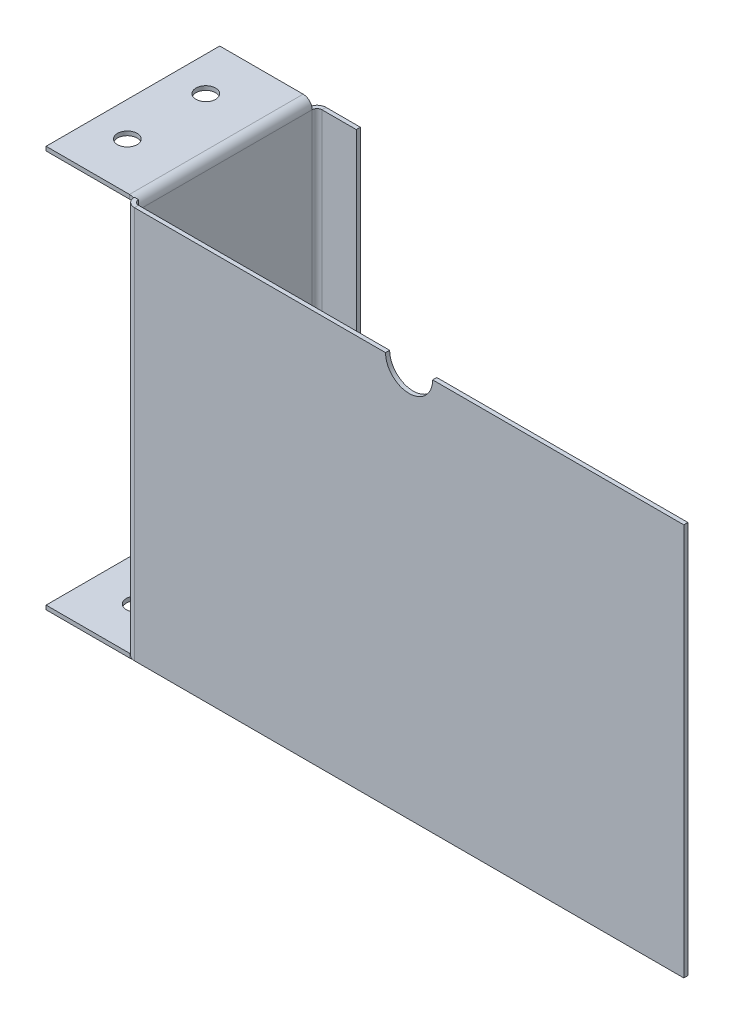
SolidWorks part; units mm, degrees
note: The reader was unsure of these and kept them because the rebuilt part matched: flange length of "Edge-Flange1", "Edge-Flange2", "Edge-Flange3", "Edge-Flange4".
material "Plain Carbon Steel"
ref_plane "Front Plane" through (0, 0, 0) normal (0, 0, 1) x (1, 0, 0)
ref_plane "Top Plane" through (0, 0, 0) normal (0, 1, 0) x (1, 0, 0)
ref_plane "Right Plane" through (0, 0, 0) normal (1, 0, 0) x (0, 0, -1)
sketch "Sketch1" plane through (0, 0, 0) normal (0, 0, 1) x (1, 0, 0)
  line L0 (0, 76.2) -> (355.6, 76.2) construction
  line L1 (0, 0) -> (355.6, 0)
  line L2 (0, 0) -> (0, 254)
  line L3 (0, 254) -> (162.56, 254)
  line L4 (355.6, 0) -> (355.6, 254)
  line L5 (177.8, 254) -> (177.8, 0) construction
  line L6 (193.04, 254) -> (355.6, 254)
  line L7 (162.56, 254) -> (177.8, 254) construction
  line L8 (177.8, 254) -> (193.04, 254) construction
  arc A0 (162.56, 254) -> (193.04, 254) centre (177.8, 254) ccw
  dimension "D4" = 15.24
  dimension "D1" = 355.6
  dimension "D2" = 254
  dimension "D3" = 177.8
base flange "Base-Flange1" sketch "Sketch1" thickness 2.6568 reverse thickness direction no parameters "D1"=3.175
edge flange "Edge-Flange1" sketch "Sketch8" flange angle 90 flange length 115.57 flange position bend outside bend radius 3.175 thickness 2.6568 relief rectangular parameters "D6"=10
sketch "Sketch8" plane through (0, 0, -2.6568) normal (-1, 0, 0) x (0, 1, 0)
  line L0 (254, 0) -> (0, 0) construction
  line L1 (254, 0) -> (0, 0)
  line L2 (0, 0) -> (0, 115.57)
  line L3 (0, 115.57) -> (254, 115.57)
  line L4 (254, 115.57) -> (254, 0)
bend "EdgeBend1" bend radius 3.175 bend angle 90 parameters "D5"=1
edge flange "Edge-Flange2" sketch "Sketch11" flange angle 90 flange length 57.15 flange position material inside bend radius 3.175 thickness 2.6568 relief none parameters "D6"=10
sketch "Sketch11" plane through (-5.8318, 254, 0) normal (0, 1, 0) x (0, 0, -1)
  line L0 (5.8318, 0) -> (118.2268, 0) construction
  line L1 (5.8318, 0) -> (118.2268, 0)
  line L2 (5.8318, 0) -> (5.8318, 57.15)
  line L3 (5.8318, 57.15) -> (118.2268, 57.15)
  line L4 (118.2268, 57.15) -> (118.2268, 0)
bend "EdgeBend2" bend radius 3.175 bend angle 90 parameters "D5"=2
edge flange "Edge-Flange3" sketch "Sketch14" flange angle 90 flange length 57.15 flange position bend outside bend radius 3.175 thickness 2.6568 relief rectangular parameters "D6"=10
sketch "Sketch14" plane through (-5.8318, 0, 0) normal (0, -1, 0) x (0, 0, 1)
  line L0 (-118.2268, 0) -> (-5.8318, 0) construction
  line L1 (-118.2268, 0) -> (-5.8318, 0)
  line L2 (-118.2268, 0) -> (-118.2268, 57.15)
  line L3 (-118.2268, 57.15) -> (-5.8318, 57.15)
  line L4 (-5.8318, 57.15) -> (-5.8318, 0)
bend "EdgeBend3" bend radius 3.175 bend angle 90 parameters "D5"=3
edge flange "Edge-Flange4" sketch "Sketch17" flange angle 90 flange length 25.4 flange position bend outside bend radius 3.175 thickness 2.6568 relief rectangular parameters "D6"=10
sketch "Sketch17" plane through (-3.175, 0, -118.2268) normal (0, 0, 1) x (0, -1, 0)
  line L2 (-248.1682, 0) -> (-248.1682, 25.4)
  line L3 (-248.1682, 25.4) -> (0, 25.4)
  line L4 (0, 25.4) -> (0, 0)
  line L5 (0, 0) -> (-248.1682, 0) construction
  line L6 (0, 0) -> (-248.1682, 0)
bend "EdgeBend4" bend radius 3.175 bend angle 90 parameters "D5"=4
sketch "Sketch22" plane through (0, 254, 0) normal (0, 1, 0) x (1, 0, 0)
  line L0 (-40.7645, 118.2268) -> (-40.7645, 5.8318) construction
  line L1 (-62.9818, 5.8318) -> (-9.0068, 5.8318) construction
  line L2 (-9.0068, 118.2268) -> (-62.9818, 118.2268) construction
  line L3 (-62.9818, 118.2268) -> (-62.9818, 5.8318) construction
  circle A0 centre (-40.7645, 86.995) radius 6.35
  circle A1 centre (-40.7645, 36.195) radius 6.35
  dimension "D2" = 12.7
  dimension "D1" = 22.2174
  dimension "D3" = 50.8
  dimension "D4" = 31.2318
extrude "Cut-Extrude1" cut sketch "Sketch22" along direction (0, -1, 0) on the side against the normal up to next (2.6568 mm away) normal cut yes
sketch "Sketch23" plane through (0, -3.175, 0) normal (0, 1, 0) x (1, 0, 0)
  line L0 (-34.4068, 118.2268) -> (-34.4068, 5.8318) construction
  line L1 (-62.9818, 118.2268) -> (-9.0068, 118.2268) construction
  line L2 (-9.0068, 5.8318) -> (-62.9818, 5.8318) construction
  line L3 (-9.0068, 118.2268) -> (-9.0068, 5.8318) construction
  circle A0 centre (-34.4068, 86.36) radius 6.35
  circle A1 centre (-34.4068, 35.56) radius 6.35
  dimension "D4" = 12.7
  dimension "D1" = 25.4
  dimension "D2" = 50.8
  dimension "D3" = 29.7282
extrude "Cut-Extrude2" cut sketch "Sketch23" along direction (0, 1, 0) on the side against the normal up to next (2.6568 mm away) normal cut yes
sketch "Sketch24" plane through (-5.8318, 0, 0) normal (-1, 0, 0) x (0, 0, 1)
  line L0 (-62.0293, 248.1682) -> (-62.0293, 76.2) construction
  line L1 (-118.2268, 248.1682) -> (-5.8318, 248.1682) construction
  line L2 (-62.0293, 76.2) -> (-62.0293, 41.7932) construction
  line L3 (-118.2268, 41.7932) -> (-5.8318, 41.7932) construction
  line L4 (-118.2268, 248.1682) -> (-118.2268, 0) construction
  line L5 (-5.8318, 248.1682) -> (-5.8318, 0) construction
  line L6 (-118.2268, 254) -> (-5.8318, 254) construction
  circle A0 centre (-86.995, 41.7932) radius 6.35
  circle A1 centre (-34.4068, 41.7932) radius 6.35
  dimension "D3" = 12.7
  dimension "D1" = 177.8
  dimension "D2" = 34.4068
  dimension "D4" = 31.2318
  dimension "D5" = 52.5882
extrude "Cut-Extrude3" cut sketch "Sketch24" along direction (1, 0, 0) on the side against the normal up to next (2.6568 mm away) normal cut yes
sketch "Bend-Lines1" [suppressed] plane through (0, 0, 0) normal (0, 1, 0) x (1, 0, 0)
sketch "Bounding-Box1" [suppressed] plane through (0, 0, 0) normal (0, 1, 0) x (1, 0, 0)
sheet metal parameters "Sheet-Metal1" thickness 2.6568 parameters "D1"=3.175
flat pattern "Flat-Pattern1" [suppressed]
sketch "Bend-Lines2" plane through (0, 0, 0) normal (0, 1, 0) x (1, 0, 0)
sketch3d "Bounding-Box2" [suppressed]
  line L0 (0, 0, 0) -> (-355.6, 0, 0) construction
  line L1 (0, 254, 0) -> (-355.6, 254, 0) construction
  line L2 (0, 0, 0) -> (0, 254, 0) construction
  line L3 (-355.6, 0, 0) -> (-355.6, 254, 0) construction
sheet metal parameters "Sheet-Metal2" thickness 2.6568 parameters "D1"=3.175
flat pattern "Flat-Pattern1"
sketch "Bend-Lines2" plane through (0, 0, 0) normal (0, 0, 1) x (1, 0, 0)
  line L0 (-3.537, 254) -> (-3.537, 0) construction
  line L1 (-3.537, 254) -> (-3.537, 0) construction
sketch3d "Bounding-Box2" [suppressed]
  line L0 (-123.5965, 0, 0) -> (355.6, 0, 0) construction
  line L1 (-123.5965, 254, 0) -> (355.6, 254, 0) construction
  line L2 (-123.5965, 0, 0) -> (-123.5965, 254, 0) construction
  line L3 (355.6, 0, 0) -> (355.6, 254, 0) construction
bend of the flat pattern "Flatten-<EdgeBend1>1"
sheet metal parameters "Sheet-Metal3" thickness 2.6568 parameters "D1"=3.175
flat pattern "Flat-Pattern1"
sketch "Bend-Lines2" plane through (0, 0, 0) normal (0, 0, 1) x (1, 0, 0)
  line L0 (-3.537, 254) -> (-3.537, 0) construction
  line L1 (-3.537, 254) -> (-3.537, 0) construction
  line L2 (-7.074, 251.7051) -> (-123.5965, 251.7051) construction
  line L3 (-7.074, 251.7051) -> (-123.5965, 251.7051) construction
sketch3d "Bounding-Box2" [suppressed]
  line L0 (-123.5965, 0, 0) -> (355.6, 0, 0) construction
  line L1 (-123.5965, 309.2171, 0) -> (355.6, 309.2171, 0) construction
  line L2 (-123.5965, 0, 0) -> (-123.5965, 309.2171, 0) construction
  line L3 (355.6, 0, 0) -> (355.6, 309.2171, 0) construction
bend of the flat pattern "Flatten-<EdgeBend1>1"
bend of the flat pattern "Flatten-<EdgeBend2>1"
sheet metal parameters "Sheet-Metal4" thickness 2.6568 parameters "D1"=3.175
flat pattern "Flat-Pattern1"
sketch "Bend-Lines2" plane through (0, 0, 0) normal (0, 0, 1) x (1, 0, 0)
  line L0 (-3.537, 254) -> (-3.537, 0) construction
  line L1 (-3.537, 254) -> (-3.537, 0) construction
  line L2 (-7.074, 251.7051) -> (-123.5965, 251.7051) construction
  line L3 (-7.074, 251.7051) -> (-123.5965, 251.7051) construction
  line L4 (-123.5965, -3.537) -> (-7.074, -3.537) construction
  line L5 (-123.5965, -3.537) -> (-7.074, -3.537) construction
sketch3d "Bounding-Box2" [suppressed]
  line L0 (-123.5965, -61.049, 0) -> (355.6, -61.049, 0) construction
  line L1 (-123.5965, 309.2171, 0) -> (355.6, 309.2171, 0) construction
  line L2 (-123.5965, -61.049, 0) -> (-123.5965, 309.2171, 0) construction
  line L3 (355.6, -61.049, 0) -> (355.6, 309.2171, 0) construction
bend of the flat pattern "Flatten-<EdgeBend1>1"
bend of the flat pattern "Flatten-<EdgeBend2>1"
bend of the flat pattern "Flatten-<EdgeBend3>1"
sheet metal parameters "Sheet-Metal5" thickness 2.6568 parameters "D1"=3.175
flat pattern "Flat-Pattern1" [suppressed]
sketch "Bend-Lines2" plane through (0, 0, 0) normal (0, 0, 1) x (1, 0, 0)
  line L0 (-3.537, 254) -> (-3.537, 0) construction
  line L1 (-3.537, 254) -> (-3.537, 0) construction
  line L2 (-7.074, 251.7051) -> (-119.469, 251.7051) construction
  line L3 (-7.074, 251.7051) -> (-119.469, 251.7051) construction
  line L4 (-119.469, -3.537) -> (-7.074, -3.537) construction
  line L5 (-119.469, -3.537) -> (-7.074, -3.537) construction
  line L6 (-123.0059, 248.1682) -> (-123.0059, 0) construction
  line L7 (-123.0059, 248.1682) -> (-123.0059, 0) construction
sketch3d "Bounding-Box2" [suppressed]
  line L0 (-326.5679, -315.049, 0) -> (177.8, -315.049, 0) construction
  line L1 (-326.5679, 55.2171, 0) -> (177.8, 55.2171, 0) construction
  line L2 (-326.5679, -315.049, 0) -> (-326.5679, 55.2171, 0) construction
  line L3 (177.8, -315.049, 0) -> (177.8, 55.2171, 0) construction
bend of the flat pattern "Flatten-<EdgeBend1>1"
bend of the flat pattern "Flatten-<EdgeBend2>1"
bend of the flat pattern "Flatten-<EdgeBend3>1"
bend of the flat pattern "Flatten-<EdgeBend4>1"
sketch "Sketch18-1" [suppressed] plane through (-1.2421, 246.2353, 0) normal (0, 0, 1) x (0, -1, 0)
  spline S2 degree 3 poles (-47.1137, -34.925) (-47.1137, -47.625) (-34.4137, -47.625) (-34.4137, -34.925) (-34.4137, -22.225) (-47.1137, -22.225) (-47.1137, -34.925) (-47.1137, -47.625) (-34.4137, -47.625) knots -0.5 0 0 0 0.5 0.5 0.5 1 1 1 1.5 1.5 1.5 weights 1 0.333333 0.333333 1 0.333333 0.333333 1 0.333333 0.333333 only from (-47.1137, -34.925) to (-47.1137, -34.925)
  spline S3 degree 3 poles (-47.1137, -86.995) (-47.1137, -99.695) (-34.4137, -99.695) (-34.4137, -86.995) (-34.4137, -74.295) (-47.1137, -74.295) (-47.1137, -86.995) (-47.1137, -99.695) (-34.4137, -99.695) knots -0.5 0 0 0 0.5 0.5 0.5 1 1 1 1.5 1.5 1.5 weights 1 0.333333 0.333333 1 0.333333 0.333333 1 0.333333 0.333333 only from (-47.1137, -86.995) to (-47.1137, -86.995)
sheet metal parameters "Sheet-Metal8" thickness 2.6568 parameters "D1"=3.175
flat pattern "Flat-Pattern1"
sketch "Bend-Lines2" plane through (0, 0, 0) normal (0, 0, 1) x (1, 0, 0)
  line L0 (-3.537, 254) -> (-3.537, 0) construction
  line L1 (-3.537, 254) -> (-3.537, 0) construction
  line L2 (-7.074, 251.7051) -> (-119.469, 251.7051) construction
  line L3 (-7.074, 251.7051) -> (-119.469, 251.7051) construction
  line L4 (-119.469, -3.537) -> (-7.074, -3.537) construction
  line L5 (-119.469, -3.537) -> (-7.074, -3.537) construction
  line L6 (-123.0059, 248.1682) -> (-123.0059, 0) construction
  line L7 (-123.0059, 248.1682) -> (-123.0059, 0) construction
sketch3d "Bounding-Box2" [suppressed]
  line L0 (-326.5679, -315.049, 0) -> (177.8, -315.049, 0) construction
  line L1 (-326.5679, 55.2171, 0) -> (177.8, 55.2171, 0) construction
  line L2 (-326.5679, -315.049, 0) -> (-326.5679, 55.2171, 0) construction
  line L3 (177.8, -315.049, 0) -> (177.8, 55.2171, 0) construction
bend of the flat pattern "Flatten-<EdgeBend1>1"
bend of the flat pattern "Flatten-<EdgeBend2>1"
bend of the flat pattern "Flatten-<EdgeBend3>1"
bend of the flat pattern "Flatten-<EdgeBend4>1"
sheet metal parameters "Sheet-Metal9" thickness 2.6568 parameters "D1"=3.175
flat pattern "Flat-Pattern1"
sketch "Bend-Lines2" plane through (0, 0, 0) normal (0, 0, 1) x (1, 0, 0)
  line L0 (-3.537, 254) -> (-3.537, 0) construction
  line L1 (-3.537, 254) -> (-3.537, 0) construction
  line L2 (-7.074, 251.7051) -> (-119.469, 251.7051) construction
  line L3 (-7.074, 251.7051) -> (-119.469, 251.7051) construction
  line L4 (-119.469, -3.537) -> (-7.074, -3.537) construction
  line L5 (-119.469, -3.537) -> (-7.074, -3.537) construction
  line L6 (-123.0059, 248.1682) -> (-123.0059, 0) construction
  line L7 (-123.0059, 248.1682) -> (-123.0059, 0) construction
sketch3d "Bounding-Box2" [suppressed]
  line L0 (-326.5679, -315.049, 0) -> (177.8, -315.049, 0) construction
  line L1 (-326.5679, 55.2171, 0) -> (177.8, 55.2171, 0) construction
  line L2 (-326.5679, -315.049, 0) -> (-326.5679, 55.2171, 0) construction
  line L3 (177.8, -315.049, 0) -> (177.8, 55.2171, 0) construction
bend of the flat pattern "Flatten-<EdgeBend1>1"
bend of the flat pattern "Flatten-<EdgeBend2>1"
bend of the flat pattern "Flatten-<EdgeBend3>1"
bend of the flat pattern "Flatten-<EdgeBend4>1"
sheet metal parameters "Sheet-Metal10" thickness 2.6568 parameters "D1"=3.175
flat pattern "Flat-Pattern1"
sketch "Bend-Lines2" plane through (0, 0, 0) normal (0, 0, 1) x (1, 0, 0)
  line L0 (-3.537, 254) -> (-3.537, 0) construction
  line L1 (-3.537, 254) -> (-3.537, 0) construction
  line L2 (-7.074, 251.7051) -> (-119.469, 251.7051) construction
  line L3 (-7.074, 251.7051) -> (-119.469, 251.7051) construction
  line L4 (-119.469, -3.537) -> (-7.074, -3.537) construction
  line L5 (-119.469, -3.537) -> (-7.074, -3.537) construction
  line L6 (-123.0059, 248.1682) -> (-123.0059, 0) construction
  line L7 (-123.0059, 248.1682) -> (-123.0059, 0) construction
sketch3d "Bounding-Box2" [suppressed]
  line L0 (-326.5679, -315.049, 0) -> (177.8, -315.049, 0) construction
  line L1 (-326.5679, 55.2171, 0) -> (177.8, 55.2171, 0) construction
  line L2 (-326.5679, -315.049, 0) -> (-326.5679, 55.2171, 0) construction
  line L3 (177.8, -315.049, 0) -> (177.8, 55.2171, 0) construction
bend of the flat pattern "Flatten-<EdgeBend1>1"
bend of the flat pattern "Flatten-<EdgeBend2>1"
bend of the flat pattern "Flatten-<EdgeBend3>1"
bend of the flat pattern "Flatten-<EdgeBend4>1"
